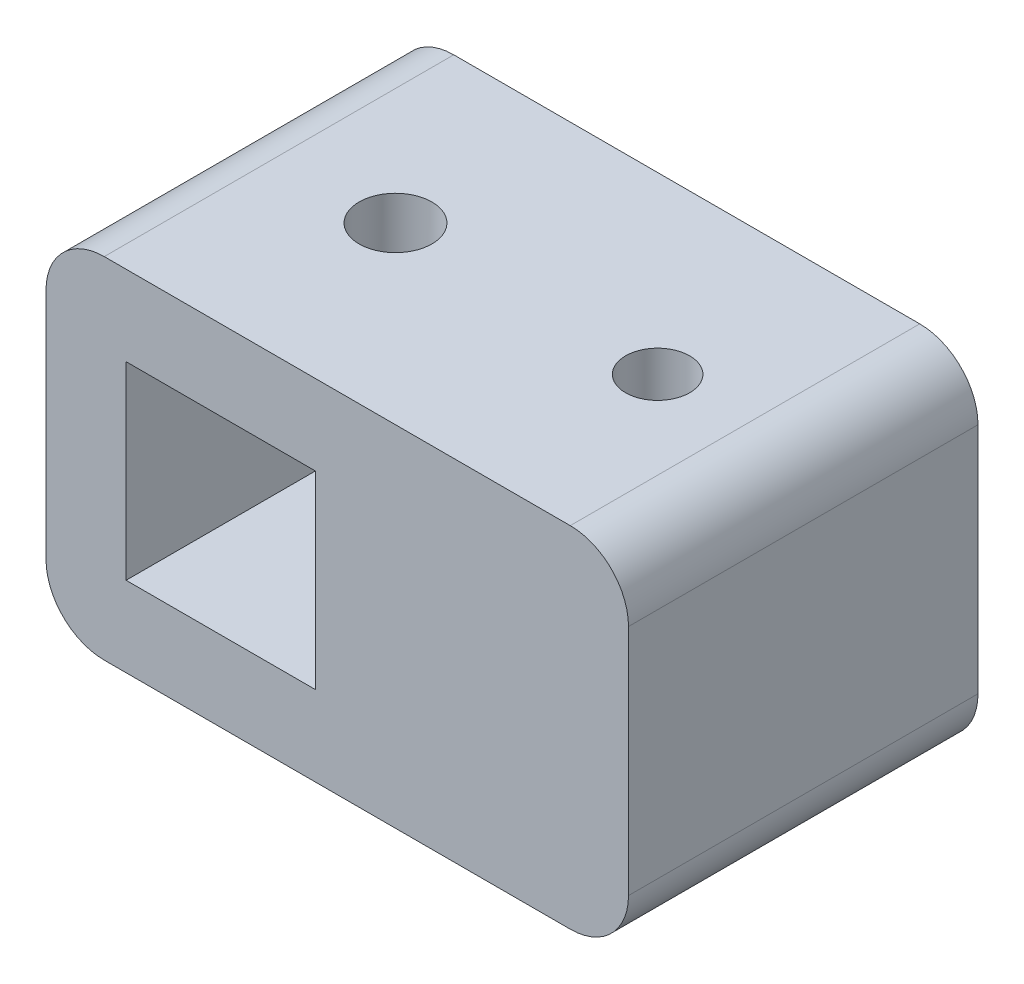
SolidWorks part; units mm, degrees
ref_plane "Front Plane" through (0, 0, 0) normal (0, 0, 1) x (1, 0, 0)
ref_plane "Top Plane" through (0, 0, 0) normal (0, 1, 0) x (1, 0, 0)
ref_plane "Right Plane" through (0, 0, 0) normal (1, 0, 0) x (0, 0, -1)
sketch "Sketch1" plane through (0, 0, 0) normal (0, 0, 1) x (1, 0, 0)
  circle A0 centre (0, 0) radius 1.25
  circle A1 centre (0, 0) radius 4.5
  dimension "D1" = 2.5
  dimension "D2" = 9
extrude "Boss-Extrude1" add sketch "Sketch1" along normal blind 8
sketch "Sketch2" plane through (0, 0, 0) normal (0, 0, -1) x (-1, 0, 0)
  circle A0 centre (0, 0) radius 1.25 construction
  circle A1 centre (0, 0) radius 4.5
  circle A2 centre (0, 0) radius 4.5
  circle A3 centre (0, 0) radius 1.25
  circle A4 centre (0, 0) radius 1.75
  circle M3 centre (0, 0) radius 1.25
  dimension "D2" = 3.5
  dimension "D1" = 0
extrude "Cut-Extrude1" cut sketch "Sketch2" against normal blind 4 contours A4 M3 region at (1.7005, 0, 0)
sketch "Sketch4" plane through (0, 0, 0) normal (0, 0, -1) x (-1, 0, 0)
  line L1 (3.25, -3.25) -> (-3.25, -3.25)
  line L2 (3.25, -3.25) -> (3.25, 3.25)
  line L3 (3.25, 3.25) -> (-3.25, 3.25)
  line L4 (-3.25, -3.25) -> (-3.25, 3.25)
  line L5 (0, 3.25) -> (0, -3.25) construction
  line L6 (3.25, 0) -> (-3.25, 0) construction
  line L7 (6, -6) -> (-6, -6)
  line L8 (6, -6) -> (6, 6)
  line L9 (6, 6) -> (-6, 6)
  line L10 (-6, -6) -> (-6, 6)
  line L11 (0, 6) -> (0, -6) construction
  line L12 (6, 0) -> (-6, 0) construction
  point P0 (0, 0)
  point P4 (0, 0)
  dimension "D1" = 6.5
  dimension "D2" = 6.5
  dimension "D3" = 12
  dimension "D4" = 12
extrude "Boss-Extrude2" add sketch "Sketch4" along normal blind 12
sketch "Sketch5" plane through (6, 0, 0) normal (1, 0, 0) x (0, 0, -1)
  line L4 (0, 6) -> (0, -6)
  line L5 (0, -6) -> (12, -6)
  line L6 (12, -6) -> (12, 6)
  line L7 (12, 6) -> (0, 6)
  line L8 (0, 6) -> (0, -6)
  line L9 (0, -6) -> (12, -6)
  line L10 (12, -6) -> (12, 6)
  line L11 (12, 6) -> (0, 6)
  dimension "D1" = 0
extrude "Boss-Extrude3" add sketch "Sketch5" along normal blind 8
sketch "Sketch6" plane through (0, 6, 0) normal (0, 1, 0) x (1, 0, 0)
  line L0 (4, 12) -> (4, 0) construction
  line L1 (4, 0) -> (14, 12) construction
  line L2 (9, 6) -> (9, 12) construction
  line L3 (9, 12) -> (9, 0) construction
  line L4 (-6, 0) -> (14, 0)
  line L5 (14, 0) -> (14, 12)
  line L6 (14, 12) -> (-6, 12)
  line L7 (-6, 12) -> (-6, 0)
  line L8 (-6, 0) -> (14, 0)
  line L9 (14, 0) -> (14, 12)
  line L10 (14, 12) -> (-6, 12)
  line L11 (-6, 12) -> (-6, 0)
  circle A1 centre (9, 6) radius 1.1
  dimension "D3" = 2.2
  dimension "D1" = 0
extrude "Cut-Extrude2" cut sketch "Sketch6" against normal through all both and the other way through all contours A1
fillet "Fillet1" radius 2 4 edges at (-6, 6, -6) (-6, -6, -6) (14, -6, -6) (14, 6, -6)
extrude "Cut-Extrude5" cut sketch "Sketch1<2>" against normal blind 8 from surface starting at face at (4.5, 0, 8)
sketch "Sketch1<2>" plane through (0, 0, 0) normal (0, 0, 1) x (1, 0, 0) same geometry as "Sketch1"
sketch "Sketch7" plane through (0, 6, 0) normal (0, 1, 0) x (1, 0, 0)
  line L0 (-3.25, 6) -> (3.25, 6) construction
  line L4 (-4, 0) -> (12, 0)
  line L5 (12, 0) -> (12, 12)
  line L6 (12, 12) -> (-4, 12)
  line L7 (-4, 12) -> (-4, 0)
  line L8 (-4, 0) -> (12, 0)
  line L9 (12, 0) -> (12, 12)
  line L10 (12, 12) -> (-4, 12)
  line L11 (-4, 12) -> (-4, 0)
  line L12 (-3.25, 0) -> (3.25, 0)
  line L13 (3.25, 0) -> (3.25, 12)
  line L14 (3.25, 12) -> (-3.25, 12)
  line L15 (-3.25, 12) -> (-3.25, 0)
  line L16 (-3.25, 0) -> (3.25, 0)
  line L17 (3.25, 0) -> (3.25, 12)
  line L18 (3.25, 12) -> (-3.25, 12)
  line L19 (-3.25, 12) -> (-3.25, 0)
  circle A0 centre (0, 6) radius 1.25
  point P12 (0, 0)
  point P13 (0, 0)
  point P15 (3.25, 5.8047)
  dimension "D3" = 2.5
  dimension "D1" = 0
  dimension "D2" = 0
extrude "Cut-Extrude6" cut sketch "Sketch7" against normal blind 13 contours A0 L0 | L0 A0 region at (0, 6, -5.4695) region at (0, 6, -6.5305)
